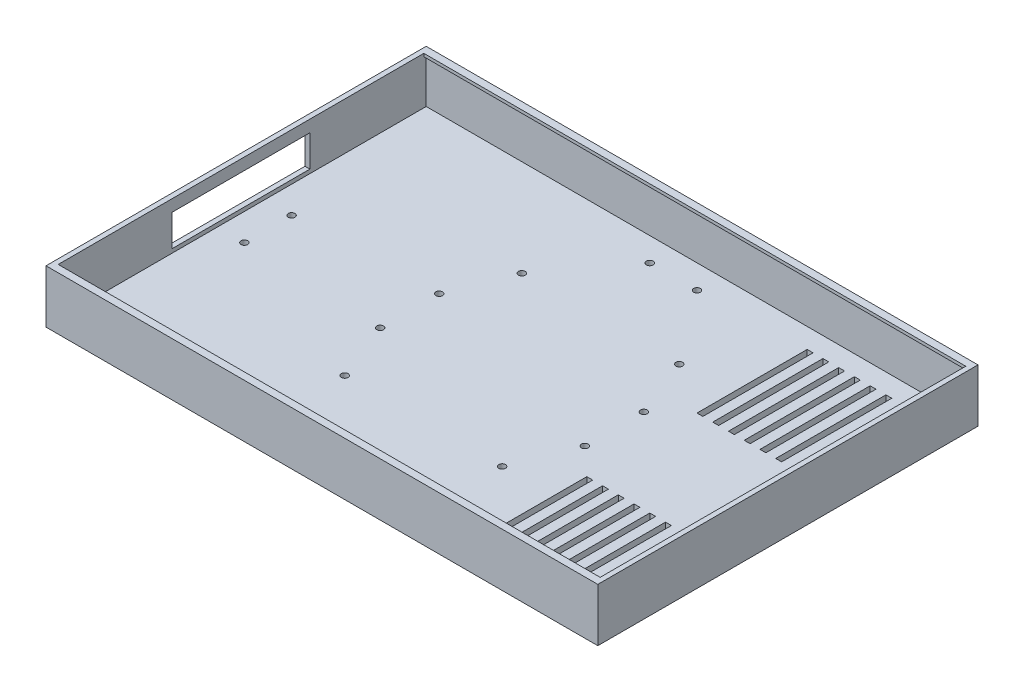
SolidWorks part; units mm, degrees
ref_plane "Front Plane" through (0, 0, 0) normal (0, 0, 1) x (1, 0, 0)
ref_plane "Top Plane" through (0, 0, 0) normal (0, 1, 0) x (1, 0, 0)
ref_plane "Right Plane" through (0, 0, 0) normal (1, 0, 0) x (0, 0, -1)
sketch "Sketch1" plane through (0, 0, 0) normal (0, 1, 0) x (1, 0, 0)
  line L1 (-140.2, -96.6) -> (140.2, -96.6)
  line L2 (-140.2, -96.6) -> (-140.2, 96.6)
  line L3 (-140.2, 96.6) -> (140.2, 96.6)
  line L4 (140.2, -96.6) -> (140.2, 96.6)
  line L5 (-140.2, -96.6) -> (140.2, 96.6) construction
  line L6 (-140.2, 96.6) -> (140.2, -96.6) construction
  point P0 (0, 0)
  dimension "D1" = 280.4
  dimension "D2" = 193.2
extrude "Shell Block" add sketch "Sketch1" along normal blind 27
ref_plane "Shell Front" through (0, 27, 0) normal (0, 1, 0) x (1, 0, 0)
sketch "Sketch2" plane through (0, 27, 0) normal (0, 1, 0) x (1, 0, 0)
  line L1 (-137.7, -92.9) -> (137.7, -92.9)
  line L2 (-137.7, -92.9) -> (-137.7, 92.9)
  line L3 (-137.7, 92.9) -> (137.7, 92.9)
  line L4 (137.7, -92.9) -> (137.7, 92.9)
  line L5 (-137.7, -92.9) -> (137.7, 92.9) construction
  line L6 (-137.7, 92.9) -> (137.7, -92.9) construction
  point P0 (0, 0)
  dimension "D1" = 275.4
  dimension "D2" = 185.8
extrude "Front Opening" cut sketch "Sketch2" against normal blind 1.5
ref_plane "Under Lip" through (0, 25.5, 0) normal (0, 1, 0) x (1, 0, 0)
sketch "Sketch3" plane through (0, 25.5, 0) normal (0, 1, 0) x (1, 0, 0)
  line L1 (-137.7, -94.1) -> (137.7, -94.1)
  line L2 (-137.7, -94.1) -> (-137.7, 94.1)
  line L3 (-137.7, 94.1) -> (137.7, 94.1)
  line L4 (137.7, -94.1) -> (137.7, 94.1)
  line L5 (-137.7, -94.1) -> (137.7, 94.1) construction
  line L6 (-137.7, 94.1) -> (137.7, -94.1) construction
  point P0 (0, 0)
  dimension "D1" = 275.4
  dimension "D2" = 188.2
extrude "Display Pocket" cut sketch "Sketch3" against normal blind 22.5
ref_plane "Back Inner" through (0, 3, 0) normal (0, 1, 0) x (1, 0, 0)
sketch "Sketch4" plane through (0, 3, 0) normal (0, 1, 0) x (1, 0, 0)
  line L1 (66, 28) -> (69, 28)
  line L2 (66, 28) -> (66, 84)
  line L3 (66, 84) -> (69, 84)
  line L4 (69, 28) -> (69, 84)
  line L6 (66, -84) -> (69, -84)
  line L7 (66, -84) -> (66, -28)
  line L8 (66, -28) -> (69, -28)
  line L9 (69, -84) -> (69, -28)
  line L11 (74, 28) -> (77, 28)
  line L12 (74, 28) -> (74, 84)
  line L13 (74, 84) -> (77, 84)
  line L14 (77, 28) -> (77, 84)
  line L16 (74, -84) -> (77, -84)
  line L17 (74, -84) -> (74, -28)
  line L18 (74, -28) -> (77, -28)
  line L19 (77, -84) -> (77, -28)
  line L21 (82, 28) -> (85, 28)
  line L22 (82, 28) -> (82, 84)
  line L23 (82, 84) -> (85, 84)
  line L24 (85, 28) -> (85, 84)
  line L26 (82, -84) -> (85, -84)
  line L27 (82, -84) -> (82, -28)
  line L28 (82, -28) -> (85, -28)
  line L29 (85, -84) -> (85, -28)
  line L31 (90, 28) -> (93, 28)
  line L32 (90, 28) -> (90, 84)
  line L33 (90, 84) -> (93, 84)
  line L34 (93, 28) -> (93, 84)
  line L36 (90, -84) -> (93, -84)
  line L37 (90, -84) -> (90, -28)
  line L38 (90, -28) -> (93, -28)
  line L39 (93, -84) -> (93, -28)
  line L41 (98, 28) -> (101, 28)
  line L42 (98, 28) -> (98, 84)
  line L43 (98, 84) -> (101, 84)
  line L44 (101, 28) -> (101, 84)
  line L46 (98, -84) -> (101, -84)
  line L47 (98, -84) -> (98, -28)
  line L48 (98, -28) -> (101, -28)
  line L49 (101, -84) -> (101, -28)
  line L51 (106, 28) -> (109, 28)
  line L52 (106, 28) -> (106, 84)
  line L53 (106, 84) -> (109, 84)
  line L54 (109, 28) -> (109, 84)
  line L56 (106, -84) -> (109, -84)
  line L57 (106, -84) -> (106, -28)
  line L58 (106, -28) -> (109, -28)
  line L59 (109, -84) -> (109, -28)
  line L61 (114, 28) -> (117, 28)
  line L62 (114, 28) -> (114, 84)
  line L63 (114, 84) -> (117, 84)
  line L64 (117, 28) -> (117, 84)
  line L66 (114, -84) -> (117, -84)
  line L67 (114, -84) -> (114, -28)
  line L68 (114, -28) -> (117, -28)
  line L69 (117, -84) -> (117, -28)
  line L71 (122, 28) -> (125, 28)
  line L72 (122, 28) -> (122, 84)
  line L73 (122, 84) -> (125, 84)
  line L74 (125, 28) -> (125, 84)
  line L76 (122, -84) -> (125, -84)
  line L77 (122, -84) -> (122, -28)
  line L78 (122, -28) -> (125, -28)
  line L79 (125, -84) -> (125, -28)
extrude "Vent Slots" cut sketch "Sketch4" against normal blind 4
sketch "Sketch5" plane through (0, 0, 0) normal (1, 0, 0) x (0, 0, -1)
  line L1 (-35, 5) -> (35, 5)
  line L2 (-35, 5) -> (-35, 21)
  line L3 (-35, 21) -> (35, 21)
  line L4 (35, 5) -> (35, 21)
extrude "Cable Exit (+X short side)" cut sketch "Sketch5" against normal blind 141.2
sketch "Sketch6" plane through (0, 3, 0) normal (0, 1, 0) x (1, 0, 0)
  circle A0 centre (-40, -45) radius 1.7
  circle A1 centre (-40, 45) radius 1.7
  circle A2 centre (40, -45) radius 1.7
  circle A3 centre (40, 45) radius 1.7
  circle A4 centre (-52, -15) radius 1.7
  circle A5 centre (-52, 15) radius 1.7
  circle A6 centre (52, -15) radius 1.7
  circle A7 centre (52, 15) radius 1.7
  circle A8 centre (-12, -82) radius 1.7
  circle A9 centre (-12, 82) radius 1.7
  circle A10 centre (12, -82) radius 1.7
  circle A11 centre (12, 82) radius 1.7
  circle A12 centre (-124, -12) radius 1.7
  circle A13 centre (-124, 12) radius 1.7
  circle A14 centre (124, -12) radius 1.7
  circle A15 centre (124, 12) radius 1.7
extrude "Bolt Holes" cut sketch "Sketch6" against normal blind 4
equation "\"DispL\" = 274.2"
equation "\"DispW\" = 187.0"
equation "\"DispT\" = 20.0"
equation "\"Clr\" = 0.6"
equation "\"Wall\" = 2.5"
equation "\"BackT\" = 3.0"
equation "\"CableRoom\" = 4.0"
equation "\"LipW\" = 1.2"
equation "\"LipT\" = 1.5"
equation "\"CableW\" = 70.0"
equation "\"CableH\" = 16.0"
equation "\"BoltD\" = 3.4"
equation "\"ShellL\" = \"DispL\" + 2 * \"Clr\" + 2 * \"Wall\""
equation "\"ShellW\" = \"DispW\" + 2 * \"Clr\" + 2 * \"Wall\""
equation "\"ShellH\" = \"BackT\" + \"DispT\" + \"CableRoom\""
equation "\"D1@Sketch1\" = \"ShellL\""
equation "\"D2@Sketch1\" = \"ShellW\""
equation "\"D1@Shell Block\" = \"ShellH\""
equation "\"D1@Shell Front\" = \"ShellH\""
equation "\"D1@Sketch2\" = \"DispL\" + 2 * \"Clr\""
equation "\"D2@Sketch2\" = \"DispW\" + 2 * \"Clr\" - 2 * \"LipW\""
equation "\"D1@Front Opening\" = \"LipT\""
equation "\"D1@Under Lip\" = \"ShellH\" - \"LipT\""
equation "\"D1@Sketch3\" = \"DispL\" + 2 * \"Clr\""
equation "\"D2@Sketch3\" = \"DispW\" + 2 * \"Clr\""
equation "\"D1@Display Pocket\" = \"ShellH\" - \"LipT\" - \"BackT\""
equation "\"D1@Back Inner\" = \"BackT\""
